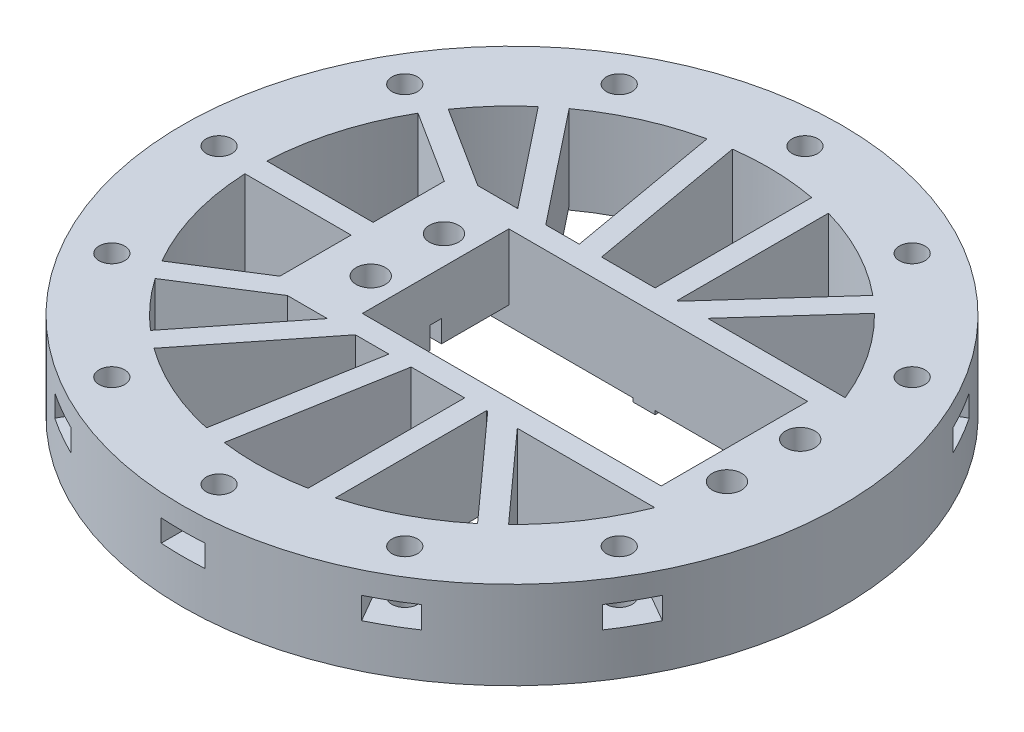
SolidWorks part; units mm, degrees
ref_plane "Front Plane" through (0, 0, 0) normal (0, 0, 1) x (1, 0, 0)
ref_plane "Top Plane" through (0, 0, 0) normal (0, 1, 0) x (1, 0, 0)
ref_plane "Right Plane" through (0, 0, 0) normal (1, 0, 0) x (0, 0, -1)
sketch "Sketch1" plane through (0, 0, 0) normal (0, 1, 0) x (1, 0, 0)
  line L0 (-43.0464, 0) -> (41.9462, 0) construction
  line L1 (0, 43.1152) -> (0, -41.8775) construction
  circle A1 centre (0, 0) radius 45
  dimension "D2" = 90
extrude "Boss-Extrude1" add sketch "Sketch1" along normal blind 12
sketch "Sketch2" plane through (0, 0, 0) normal (0, -1, 0) x (1, 0, 0)
  circle A0 centre (0, 0) radius 35
  dimension "D1" = 70
extrude "Cut-Extrude1" cut sketch "Sketch2" against normal blind 0.5
sketch "Sketch3" plane through (0, 0.5, 0) normal (0, -1, 0) x (1, 0, 0)
  line L0 (35, 0) -> (-35, 0) construction
  line L1 (0, -35) -> (0, 35) construction
  line L3 (37.5324, -10) -> (-17.4676, -10)
  line L4 (37.5324, -10) -> (37.5324, 10)
  line L5 (37.5324, 10) -> (-17.4676, 10)
  line L6 (-17.4676, -10) -> (-17.4676, 10)
  circle A0 centre (0, 0) radius 35 construction
  circle A1 centre (0, 0) radius 35 construction
  dimension "D1" = 20
  dimension "D2" = 55
  dimension "D3" = 10
  dimension "D4" = 37.5324
extrude "Cut-Extrude2" cut sketch "Sketch3" against normal blind 2.5 and the other way up to next
sketch "Sketch4" plane through (0, 3, 0) normal (0, -1, 0) x (1, 0, 0)
  line L0 (37.5324, 0) -> (-17.4676, 0) construction
  line L1 (37.5324, 10) -> (37.5324, -10) construction
  line L2 (-17.4676, 10) -> (-17.4676, -10) construction
  line L3 (0, -10) -> (0, 10) construction
  line L4 (-17.4676, -10) -> (33.541, -10) construction
  line L5 (33.541, 10) -> (-17.4676, 10) construction
  line L7 (30.3722, -10) -> (-10.4278, -10)
  line L8 (30.3722, -10) -> (30.3722, 10)
  line L9 (30.3722, 10) -> (-10.4278, 10)
  line L10 (-10.4278, -10) -> (-10.4278, 10)
  dimension "D1" = 20
  dimension "D2" = 40.8
  dimension "D3" = 30.3722
  dimension "D4" = 10
extrude "Cut-Extrude3" cut sketch "Sketch4" against normal blind 9
sketch "Sketch8" plane through (0, 0.5, 0) normal (0, -1, 0) x (1, 0, 0)
  line L0 (-17.4676, 0) -> (-35, 0) construction
  line L1 (-17.4676, 10) -> (-17.4676, -10) construction
  line L2 (8.0367, 10) -> (8.0367, 34.0648) construction
  line L3 (33.541, 10) -> (-17.4676, 10) construction
  line L4 (8.0367, -10) -> (8.0367, -29.3194) construction
  line L5 (-17.4676, -10) -> (33.541, -10) construction
  line L6 (6.5367, 10) -> (6.5367, 34.3842)
  line L7 (9.5367, 10) -> (9.5367, 33.6757)
  line L8 (9.5367, 10) -> (6.5367, 10)
  line L9 (9.5367, -10) -> (6.5367, -10)
  line L10 (6.5367, -10) -> (6.5367, -34.3842)
  line L11 (9.5367, -10) -> (9.5367, -33.6757)
  line L12 (-17.4676, 1.5) -> (-34.9678, 1.5)
  line L13 (-17.4676, -1.5) -> (-34.9678, -1.5)
  line L14 (-17.4676, 1.5) -> (-17.4676, -1.5)
  arc A0 (33.541, 10) -> (33.541, -10) centre (0, 0) ccw construction
  arc A1 (9.5367, 33.6757) -> (6.5367, 34.3842) centre (7.9531, 33.6757) ccw
  arc A2 (9.5367, -33.6757) -> (6.5367, -34.3842) centre (7.9531, -33.6757) cw
  arc A3 (-34.9678, 1.5) -> (-34.9678, -1.5) centre (-34.9678, 0) ccw
  dimension "D3" = 1.5
  dimension "D1" = 1.5
  dimension "D2" = 1.5
  dimension "D4" = 1.5
extrude "Boss-Extrude2" add sketch "Sketch8" along normal through all
sketch "Sketch16" plane through (0, 3, 0) normal (0, -1, 0) x (1, 0, 0)
  line L0 (-17.4676, 0) -> (37.5324, 0) construction
  line L1 (-17.4676, 10) -> (-17.4676, -10) construction
  line L2 (37.5324, -10) -> (37.5324, 10) construction
  line L3 (30.3722, -0.8) -> (37.5324, -0.8)
  line L4 (-10.4278, -0.8) -> (-17.4676, -0.8)
  line L5 (-10.4278, 10) -> (-10.4278, -10) construction
  line L6 (-10.4278, 0.8) -> (-17.4676, 0.8)
  line L7 (-17.4676, 0.8) -> (-17.4676, -0.8)
  line L8 (-10.4278, 0.8) -> (-10.4278, -0.8)
  line L9 (30.3722, -10) -> (30.3722, 10) construction
  line L10 (30.3722, 0.8) -> (37.5324, 0.8)
  line L11 (37.5324, 0.8) -> (37.5324, -0.8)
  line L12 (30.3722, 0.8) -> (30.3722, -0.8)
  dimension "D1" = 0.8
extrude "Cut-Extrude10" cut sketch "Sketch16" against normal blind 3
sketch "Sketch27" plane through (0, 0, 0) normal (0, -1, 0) x (1, 0, 0)
  line L0 (0, 0) -> (0, -53.17) construction
  line L1 (0, 0) -> (47.7582, -27.5732) construction
  line L3 (31.641, -18.2679) -> (31.641, -21.7321) construction
  line L4 (31.641, -21.7321) -> (34.641, -23.4641) construction
  line L5 (34.641, -23.4641) -> (37.641, -21.7321) construction
  line L6 (37.641, -21.7321) -> (37.641, -18.2679) construction
  line L7 (37.641, -18.2679) -> (34.641, -16.5359) construction
  line L8 (34.641, -16.5359) -> (31.641, -18.2679) construction
  circle A0 centre (0, 0) radius 40 construction
  circle A1 centre (34.641, -20) radius 1.75
  circle A2 centre (0, 0) radius 35 construction
  circle A3 centre (34.641, -20) radius 3 construction
  circle A4 centre (20, -34.641) radius 1.75
  circle A5 centre (0, -40) radius 1.75
  circle A6 centre (-20, -34.641) radius 1.75
  circle A7 centre (-34.641, -20) radius 1.75
  circle A8 centre (-40, 0) radius 1.75
  circle A9 centre (-34.641, 20) radius 1.75
  circle A10 centre (-20, 34.641) radius 1.75
  circle A11 centre (0, 40) radius 1.75
  circle A12 centre (20, 34.641) radius 1.75
  circle A13 centre (34.641, 20) radius 1.75
  circle A15 centre (40, 0) radius 1.75 [skipped]
  point P28 (0, 0)
  point P41 (0, 0)
  dimension "D1" = 80
  dimension "D3" = 3.5
  dimension "D4" = 70
  dimension "D5" = 6
  dimension "D6" = 12
  dimension "D2" = 60
extrude "Cut-Extrude15" cut sketch "Sketch27" against normal through all
ref_plane "Plane1" through (0, 9, 0) normal (0, 1, 0) x (1, 0, 0)
sketch "Sketch28" plane through (0, 9, 0) normal (0, 1, 0) x (1, 0, 0)
  line L0 (0, 0) -> (-54.493, 0) construction
  line L1 (-31.641, 18.2679) -> (-31.641, 21.7321)
  line L2 (-36.5359, 0) -> (-38.2679, 3)
  line L3 (-38.2679, 3) -> (-44.8999, 3)
  line L4 (-31.641, 21.7321) -> (-37.3844, 25.048)
  line L5 (-40.3844, 19.8519) -> (-34.641, 16.5359)
  line L6 (-44.8999, -3) -> (-38.2679, -3)
  line L7 (-38.2679, -3) -> (-36.5359, 0)
  line L8 (-43.4641, 0) -> (-42.5981, -1.5) [skipped]
  line L9 (-41.7321, 3) -> (-42.5981, 1.5) [skipped]
  line L10 (-34.641, 16.5359) -> (-31.641, 18.2679)
  line L11 (-18.2679, 31.641) -> (-16.5359, 34.641)
  line L12 (-16.5359, 34.641) -> (-19.8519, 40.3844)
  line L13 (-25.048, 37.3844) -> (-21.7321, 31.641)
  line L14 (-21.7321, 31.641) -> (-18.2679, 31.641)
  line L15 (0, 36.5359) -> (3, 38.2679)
  line L16 (3, 38.2679) -> (3, 44.8999)
  line L17 (-3, 44.8999) -> (-3, 38.2679)
  line L18 (-3, 38.2679) -> (0, 36.5359)
  line L19 (18.2679, 31.641) -> (21.7321, 31.641)
  line L20 (21.7321, 31.641) -> (25.048, 37.3844)
  line L21 (19.8519, 40.3844) -> (16.5359, 34.641)
  line L22 (16.5359, 34.641) -> (18.2679, 31.641)
  line L23 (31.641, 18.2679) -> (34.641, 16.5359)
  line L24 (34.641, 16.5359) -> (40.3844, 19.8519)
  line L25 (37.3844, 25.048) -> (31.641, 21.7321)
  line L26 (31.641, 21.7321) -> (31.641, 18.2679)
  line L31 (31.641, -18.2679) -> (31.641, -21.7321)
  line L32 (31.641, -21.7321) -> (37.3844, -25.048)
  line L33 (40.3844, -19.8519) -> (34.641, -16.5359)
  line L34 (34.641, -16.5359) -> (31.641, -18.2679)
  line L35 (18.2679, -31.641) -> (16.5359, -34.641)
  line L36 (16.5359, -34.641) -> (19.8519, -40.3844)
  line L37 (25.048, -37.3844) -> (21.7321, -31.641)
  line L38 (21.7321, -31.641) -> (18.2679, -31.641)
  line L39 (0, -36.5359) -> (-3, -38.2679)
  line L40 (-3, -38.2679) -> (-3, -44.8999)
  line L41 (3, -44.8999) -> (3, -38.2679)
  line L42 (3, -38.2679) -> (0, -36.5359)
  line L43 (-18.2679, -31.641) -> (-21.7321, -31.641)
  line L44 (-21.7321, -31.641) -> (-25.048, -37.3844)
  line L45 (-19.8519, -40.3844) -> (-16.5359, -34.641)
  line L46 (-16.5359, -34.641) -> (-18.2679, -31.641)
  line L47 (-31.641, -18.2679) -> (-34.641, -16.5359)
  line L48 (-34.641, -16.5359) -> (-40.3844, -19.8519)
  line L49 (-37.3844, -25.048) -> (-31.641, -21.7321)
  line L50 (-31.641, -21.7321) -> (-31.641, -18.2679)
  line L51 (36.5359, 0) -> (38.2679, -3) [skipped]
  line L52 (38.2679, -3) -> (44.8999, -3) [skipped]
  line L53 (44.8999, 3) -> (38.2679, 3) [skipped]
  line L54 (38.2679, 3) -> (36.5359, 0) [skipped]
  arc A0 (-44.8999, 3) -> (-44.8999, -3) centre (0, 0) ccw
  circle A1 centre (-40, 0) radius 3 construction
  arc A2 (-37.3844, 25.048) -> (-40.3844, 19.8519) centre (0, 0) ccw
  circle A3 centre (-34.641, 20) radius 3 construction
  arc A4 (-19.8519, 40.3844) -> (-25.048, 37.3844) centre (0, 0) ccw
  circle A5 centre (-20, 34.641) radius 3 construction
  arc A6 (3, 44.8999) -> (-3, 44.8999) centre (0, 0) ccw
  circle A7 centre (0, 40) radius 3 construction
  arc A8 (25.048, 37.3844) -> (19.8519, 40.3844) centre (0, 0) ccw
  circle A9 centre (20, 34.641) radius 3 construction
  arc A10 (40.3844, 19.8519) -> (37.3844, 25.048) centre (0, 0) ccw
  circle A11 centre (34.641, 20) radius 3 construction
  arc A14 (37.3844, -25.048) -> (40.3844, -19.8519) centre (0, 0) ccw
  circle A15 centre (34.641, -20) radius 3 construction
  arc A16 (19.8519, -40.3844) -> (25.048, -37.3844) centre (0, 0) ccw
  circle A17 centre (20, -34.641) radius 3 construction
  arc A18 (-3, -44.8999) -> (3, -44.8999) centre (0, 0) ccw
  circle A19 centre (0, -40) radius 3 construction
  arc A20 (-25.048, -37.3844) -> (-19.8519, -40.3844) centre (0, 0) ccw
  circle A21 centre (-20, -34.641) radius 3 construction
  arc A22 (-40.3844, -19.8519) -> (-37.3844, -25.048) centre (0, 0) ccw
  circle A23 centre (-34.641, -20) radius 3 construction
  arc A24 (44.8999, -3) -> (44.8999, 3) centre (0, 0) ccw [skipped]
  circle A25 centre (40, 0) radius 3 construction
  point P94 (0, 0)
  dimension "D1" = 90
  dimension "D2" = 6
  dimension "D3" = 12
extrude "Cut-Extrude17" cut sketch "Sketch28" against normal blind 3
sketch "Sketch29" plane through (0, 0.5, 0) normal (0, -1, 0) x (1, 0, 0)
  line L0 (32.4962, -13) -> (13.7255, -13)
  line L1 (9.5367, -33.6757) -> (9.5367, -10) construction
  line L2 (9.5367, -13) -> (9.5367, -33.6757)
  line L3 (9.5367, -10) -> (33.541, -10) construction
  line L4 (6.5367, -13) -> (-0.7691, -13)
  line L5 (6.5367, -10) -> (6.5367, -34.3842) construction
  line L6 (-20.4676, -11.223) -> (-20.4676, -1.5)
  line L7 (-34.9678, -1.5) -> (-17.4676, -1.5) construction
  line L8 (-20.4676, -1.5) -> (-34.9678, -1.5)
  line L9 (-17.4676, -0.8) -> (-17.4676, -10) construction
  line L10 (32.4962, 13) -> (13.7255, 13)
  line L11 (9.5367, 10) -> (9.5367, 33.6757) construction
  line L12 (9.5367, 13) -> (9.5367, 33.6757)
  line L13 (-7.5493, 34.1761) -> (-3.8154, 13)
  line L14 (6.5367, 13) -> (-0.7691, 13)
  line L15 (6.5367, 34.3842) -> (6.5367, 10) construction
  line L16 (-20.4676, 11.223) -> (-20.4676, 1.5)
  line L17 (-17.4676, 1.5) -> (-34.9678, 1.5) construction
  line L18 (-20.4676, 1.5) -> (-34.9678, 1.5)
  line L19 (6.5367, 13) -> (6.5367, 34.3842)
  line L20 (6.5367, -34.3842) -> (6.5367, -13)
  line L21 (0, 0) -> (-21.7353, -27.4331) construction
  line L22 (-20.5397, -28.3394) -> (-8.3862, -13)
  line L23 (-22.8911, -26.4764) -> (-12.2137, -13)
  line L24 (0, 0) -> (-20.4676, -13) construction
  line L25 (-17.6698, -13) -> (-28.713, -20.0141)
  line L26 (-20.4676, -11.223) -> (-30.3215, -17.4817)
  line L27 (0, 0) -> (-35, 0) construction
  line L28 (-20.4676, 11.223) -> (-30.3215, 17.4817)
  line L29 (-17.6698, 13) -> (-28.713, 20.0141)
  line L30 (-22.8911, 26.4764) -> (-12.2137, 13)
  line L31 (-20.5397, 28.3394) -> (-8.3862, 13)
  line L32 (-12.2137, 13) -> (-17.6698, 13)
  line L33 (0, 0) -> (-6.0777, -34.4683) construction
  line L34 (-4.5949, -34.6971) -> (-0.7691, -13)
  line L35 (-7.5493, -34.1761) -> (-3.8154, -13)
  line L36 (-3.8154, -13) -> (-17.6698, -13)
  line L37 (-4.5949, 34.6971) -> (-0.7691, 13)
  line L38 (-3.8154, 13) -> (-8.3862, 13)
  line L39 (0, 0) -> (23.4214, -26.0084) construction
  line L40 (9.6883, -13) -> (22.2852, -26.9883)
  line L41 (13.7255, -13) -> (24.5145, -24.9808)
  line L42 (13.7255, 13) -> (24.5145, 24.9808)
  line L43 (9.6883, 13) -> (22.2852, 26.9883)
  line L44 (9.6883, -13) -> (9.5367, -13)
  line L45 (9.6883, 13) -> (9.5367, 13)
  arc A0 (9.5367, -33.6757) -> (22.2852, -26.9883) centre (0, 0) ccw
  arc A1 (6.5367, 34.3842) -> (-4.5949, 34.6971) centre (0, 0) ccw
  arc A2 (32.4962, 13) -> (24.5145, 24.9808) centre (0, 0) ccw
  arc A3 (-34.9678, -1.5) -> (-30.3215, -17.4817) centre (0, 0) ccw
  circle A4 centre (0, 0) radius 35 construction
  arc A5 (-7.5493, 34.1761) -> (-20.5397, 28.3394) centre (0, 0) ccw
  arc A6 (-4.5949, -34.6971) -> (6.5367, -34.3842) centre (0, 0) ccw
  arc A7 (-20.5397, -28.3394) -> (-7.5493, -34.1761) centre (0, 0) ccw
  arc A8 (-28.713, -20.0141) -> (-22.8911, -26.4764) centre (0, 0) ccw
  arc A9 (-30.3215, 17.4817) -> (-34.9678, 1.5) centre (0, 0) ccw
  arc A10 (-22.8911, 26.4764) -> (-28.713, 20.0141) centre (0, 0) ccw
  arc A11 (24.5145, -24.9808) -> (32.4962, -13) centre (0, 0) ccw
  arc A12 (22.2852, 26.9883) -> (9.5367, 33.6757) centre (0, 0) ccw
  point P11 (21.5389, -10)
  point P23 (-17.4676, -5.4)
  line M3 (-17.4676, -1.5) -> (-34.9678, -1.5)
  arc M4 (-34.9678, -1.5) -> (6.5367, -34.3842) centre (0, 0) ccw
  line M5 (6.5367, -34.3842) -> (6.5367, -10)
  dimension "D1" = 1.5
  dimension "D2" = 3
  dimension "D3" = 3
  dimension "D4" = 80
  dimension "D5" = 1.5
  dimension "D6" = 1.5
  dimension "D7" = 1.5
sketch "Sketch32" plane through (0, 3, 0) normal (0, -1, 0) x (1, 0, 0)
  line L0 (-17.4676, 0) -> (37.5324, 0) construction
  line L1 (-17.4676, -1.5) -> (-17.4676, 1.5) construction
  line L2 (37.5324, 10) -> (37.5324, -10) construction
  line L3 (10.0324, 0) -> (10.0324, -10) construction
  line L6 (9.5367, -10) -> (33.541, -10) construction
  circle A0 centre (-14.2876, -5) radius 2
  circle A1 centre (-14.2876, 5) radius 2
  circle A2 centre (34.3524, -5) radius 2
  circle A3 centre (34.3524, 5) radius 2
  dimension "D1" = 24.32
  dimension "D3" = 4
  dimension "D2" = 5
extrude "Cut-Extrude21" cut sketch "Sketch32" against normal through all
extrude "Cut-Extrude22" cut sketch "Sketch29" against normal blind 12 contours L28 A9 L18 L16 | L26 L6 M3 M4 | L23 L36 L25 M4 | L35 L36 L22 M4 | L34 L4 M4 M5 | L2 A0 L40 L44 | L41 A11 L0 | L10 A2 L42 | L43 A12 L12 L45 | L19 A1 L37 L14 | L13 A5 L31 L38 | L30 A10 L29 L32 region at (23.89, 0.5, -17.1237) region at (13.9029, 0.5, -24.813) region at (1.8383, 0.5, -24.6789) region at (-27.5459, 0.5, -7.8919) region at (-10.8152, 0.5, -24.1049) region at (-20.9968, 0.5, -18.9781) region at (23.89, 0.5, 17.1237) region at (13.9029, 0.5, 24.813) region at (-10.8152, 0.5, 24.1049) region at (1.8383, 0.5, 24.6789) region at (-27.5459, 0.5, 7.8919) region at (-20.9968, 0.5, 18.9781)
